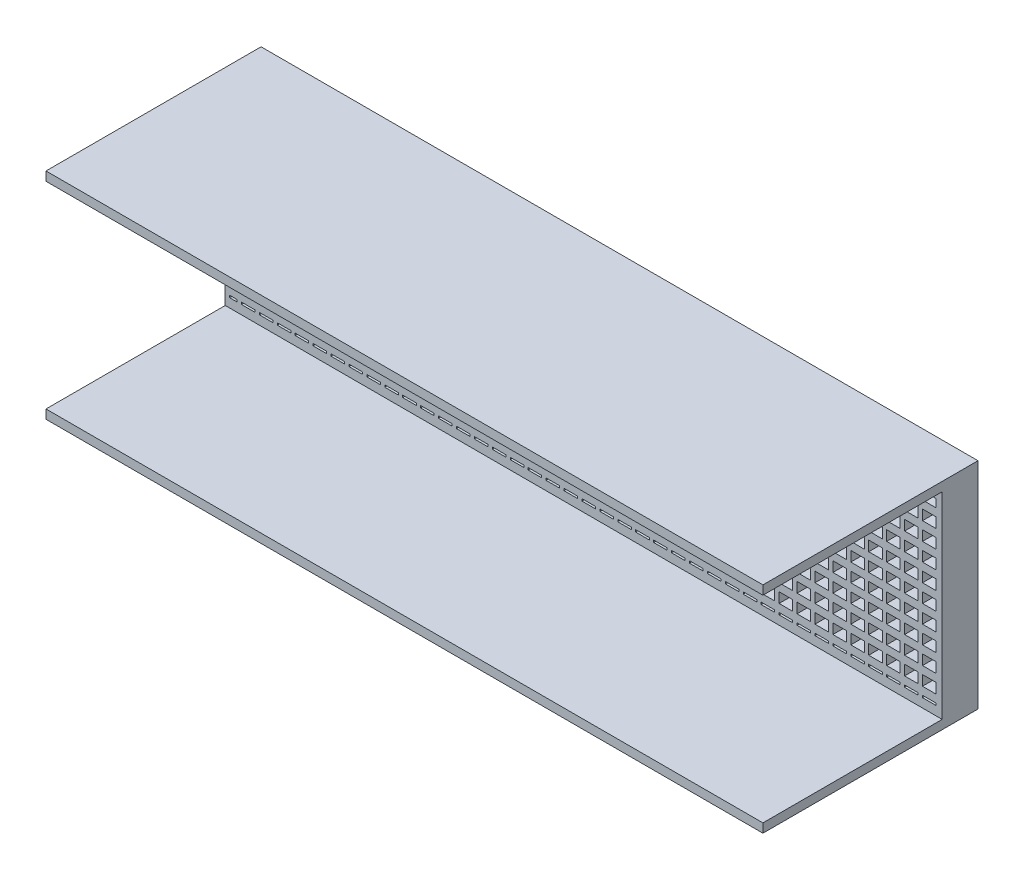
SolidWorks part; units mm, degrees
ref_plane "Plan de face" through (0, 0, 0) normal (0, 0, 1) x (1, 0, 0)
ref_plane "Plan de dessus" through (0, 0, 0) normal (0, 1, 0) x (1, 0, 0)
ref_plane "Plan de droite" through (0, 0, 0) normal (1, 0, 0) x (0, 0, -1)
sketch "Esquisse1" plane through (0, 0, 0) normal (0, 0, 1) x (1, 0, 0)
  line L1 (-200, 60) -> (200, 60)
  line L2 (-200, 60) -> (-200, -60)
  line L3 (-200, -60) -> (200, -60)
  line L4 (200, 60) -> (200, -60)
  line L5 (-200, 60) -> (200, -60) construction
  line L6 (-200, -60) -> (200, 60) construction
  line L7 (-197.5, 50) -> (197.5, 50)
  line L8 (-197.5, 50) -> (-197.5, -50)
  line L9 (-197.5, -50) -> (197.5, -50)
  line L10 (197.5, 50) -> (197.5, -50)
  line L11 (-197.5, 50) -> (197.5, -50) construction
  line L12 (-197.5, -50) -> (197.5, 50) construction
  point P0 (0, 0)
  point P6 (0, 0)
  dimension "D1" = 120
  dimension "D2" = 400
  dimension "D3" = 100
  dimension "D4" = 395
extrude "Boss.-Extru.1" add sketch "Esquisse1" along normal blind 120
sketch "Esquisse2" plane through (200, 0, 0) normal (1, 0, 0) x (0, 0, -1)
  line L0 (-135.8459, 0) -> (-4.1541, 0)
  line L5 (0, -60) -> (0, 60) construction
  line L6 (-120, 55) -> (-20, 55)
  line L7 (-120, 55) -> (-120, -55)
  line L8 (-120, -55) -> (-20, -55)
  line L9 (-20, 55) -> (-20, -55)
  line L10 (-120, 55) -> (-20, -55) construction
  line L11 (-120, -55) -> (-20, 55) construction
  point P11 (-70, 0)
  line M3 (-120, 60) -> (-120, -60)
  dimension "D1" = 100
  dimension "D2" = 20
  dimension "D3" = 110
extrude "Enlèv. mat.-Extru.1" cut sketch "Esquisse2" against normal through all both and the other way through all contours L9 L0 L8 M3 | L9 L6 L0 M3
sketch "Esquisse3" plane through (0, 0, 0) normal (0, 0, 1) x (1, 0, 0)
  line L0 (0, 113.9333) -> (0, -153.2626) construction
  line L1 (-197.5, -50) -> (197.5, -50) construction
  line L2 (-193.4028, 50) -> (-190.97, 50)
  line L3 (-193.4028, 50) -> (-193.4028, -50)
  line L4 (-193.4028, -50) -> (-190.97, -50)
  line L5 (-190.97, 50) -> (-190.97, -50)
  line L6 (-193.4028, 50) -> (-190.97, -50) construction
  line L7 (-193.4028, -50) -> (-190.97, 50) construction
  line L8 (-197.5, 0) -> (197.5, 0) construction
  line L9 (-197.5, 50) -> (-197.5, -50) construction
  line L10 (197.5, -50) -> (197.5, 50) construction
  line L11 (-180.97, 50) -> (-180.97, -50)
  line L12 (-183.4028, 50) -> (-183.4028, -50)
  line L13 (-183.4028, -50) -> (-180.97, -50)
  line L14 (-183.4028, 50) -> (-180.97, 50)
  line L15 (-170.97, 50) -> (-170.97, -50)
  line L16 (-173.4028, 50) -> (-173.4028, -50)
  line L17 (-173.4028, -50) -> (-170.97, -50)
  line L18 (-173.4028, 50) -> (-170.97, 50)
  line L19 (-160.97, 50) -> (-160.97, -50)
  line L20 (-163.4028, 50) -> (-163.4028, -50)
  line L21 (-163.4028, -50) -> (-160.97, -50)
  line L22 (-163.4028, 50) -> (-160.97, 50)
  line L23 (-150.97, 50) -> (-150.97, -50)
  line L24 (-153.4028, 50) -> (-153.4028, -50)
  line L25 (-153.4028, -50) -> (-150.97, -50)
  line L26 (-153.4028, 50) -> (-150.97, 50)
  line L27 (-140.97, 50) -> (-140.97, -50)
  line L28 (-143.4028, 50) -> (-143.4028, -50)
  line L29 (-143.4028, -50) -> (-140.97, -50)
  line L30 (-143.4028, 50) -> (-140.97, 50)
  line L31 (-130.97, 50) -> (-130.97, -50)
  line L32 (-133.4028, 50) -> (-133.4028, -50)
  line L33 (-133.4028, -50) -> (-130.97, -50)
  line L34 (-133.4028, 50) -> (-130.97, 50)
  line L35 (-120.97, 50) -> (-120.97, -50)
  line L36 (-123.4028, 50) -> (-123.4028, -50)
  line L37 (-123.4028, -50) -> (-120.97, -50)
  line L38 (-123.4028, 50) -> (-120.97, 50)
  line L39 (-110.97, 50) -> (-110.97, -50)
  line L40 (-113.4028, 50) -> (-113.4028, -50)
  line L41 (-113.4028, -50) -> (-110.97, -50)
  line L42 (-113.4028, 50) -> (-110.97, 50)
  line L43 (-100.97, 50) -> (-100.97, -50)
  line L44 (-103.4028, 50) -> (-103.4028, -50)
  line L45 (-103.4028, -50) -> (-100.97, -50)
  line L46 (-103.4028, 50) -> (-100.97, 50)
  line L47 (-90.97, 50) -> (-90.97, -50)
  line L48 (-93.4028, 50) -> (-93.4028, -50)
  line L49 (-93.4028, -50) -> (-90.97, -50)
  line L50 (-93.4028, 50) -> (-90.97, 50)
  line L51 (-80.97, 50) -> (-80.97, -50)
  line L52 (-83.4028, 50) -> (-83.4028, -50)
  line L53 (-83.4028, -50) -> (-80.97, -50)
  line L54 (-83.4028, 50) -> (-80.97, 50)
  line L55 (-70.97, 50) -> (-70.97, -50)
  line L56 (-73.4028, 50) -> (-73.4028, -50)
  line L57 (-73.4028, -50) -> (-70.97, -50)
  line L58 (-73.4028, 50) -> (-70.97, 50)
  line L59 (-60.97, 50) -> (-60.97, -50)
  line L60 (-63.4028, 50) -> (-63.4028, -50)
  line L61 (-63.4028, -50) -> (-60.97, -50)
  line L62 (-63.4028, 50) -> (-60.97, 50)
  line L63 (-50.97, 50) -> (-50.97, -50)
  line L64 (-53.4028, 50) -> (-53.4028, -50)
  line L65 (-53.4028, -50) -> (-50.97, -50)
  line L66 (-53.4028, 50) -> (-50.97, 50)
  line L67 (-40.97, 50) -> (-40.97, -50)
  line L68 (-43.4028, 50) -> (-43.4028, -50)
  line L69 (-43.4028, -50) -> (-40.97, -50)
  line L70 (-43.4028, 50) -> (-40.97, 50)
  line L71 (-30.97, 50) -> (-30.97, -50)
  line L72 (-33.4028, 50) -> (-33.4028, -50)
  line L73 (-33.4028, -50) -> (-30.97, -50)
  line L74 (-33.4028, 50) -> (-30.97, 50)
  line L75 (-20.97, 50) -> (-20.97, -50)
  line L76 (-23.4028, 50) -> (-23.4028, -50)
  line L77 (-23.4028, -50) -> (-20.97, -50)
  line L78 (-23.4028, 50) -> (-20.97, 50)
  line L79 (-10.97, 50) -> (-10.97, -50)
  line L80 (-13.4028, 50) -> (-13.4028, -50)
  line L81 (-13.4028, -50) -> (-10.97, -50)
  line L82 (-13.4028, 50) -> (-10.97, 50)
  line L83 (-0.97, 50) -> (-0.97, -50)
  line L84 (-3.4028, 50) -> (-3.4028, -50)
  line L85 (-3.4028, -50) -> (-0.97, -50)
  line L86 (-3.4028, 50) -> (-0.97, 50)
  line L87 (9.03, 50) -> (9.03, -50)
  line L88 (6.5972, 50) -> (6.5972, -50)
  line L89 (6.5972, -50) -> (9.03, -50)
  line L90 (6.5972, 50) -> (9.03, 50)
  line L91 (19.03, 50) -> (19.03, -50)
  line L92 (16.5972, 50) -> (16.5972, -50)
  line L93 (16.5972, -50) -> (19.03, -50)
  line L94 (16.5972, 50) -> (19.03, 50)
  line L95 (29.03, 50) -> (29.03, -50)
  line L96 (26.5972, 50) -> (26.5972, -50)
  line L97 (26.5972, -50) -> (29.03, -50)
  line L98 (26.5972, 50) -> (29.03, 50)
  line L99 (39.03, 50) -> (39.03, -50)
  line L100 (36.5972, 50) -> (36.5972, -50)
  line L101 (36.5972, -50) -> (39.03, -50)
  line L102 (36.5972, 50) -> (39.03, 50)
  line L103 (49.03, 50) -> (49.03, -50)
  line L104 (46.5972, 50) -> (46.5972, -50)
  line L105 (46.5972, -50) -> (49.03, -50)
  line L106 (46.5972, 50) -> (49.03, 50)
  line L107 (59.03, 50) -> (59.03, -50)
  line L108 (56.5972, 50) -> (56.5972, -50)
  line L109 (56.5972, -50) -> (59.03, -50)
  line L110 (56.5972, 50) -> (59.03, 50)
  line L111 (69.03, 50) -> (69.03, -50)
  line L112 (66.5972, 50) -> (66.5972, -50)
  line L113 (66.5972, -50) -> (69.03, -50)
  line L114 (66.5972, 50) -> (69.03, 50)
  line L115 (79.03, 50) -> (79.03, -50)
  line L116 (76.5972, 50) -> (76.5972, -50)
  line L117 (76.5972, -50) -> (79.03, -50)
  line L118 (76.5972, 50) -> (79.03, 50)
  line L119 (89.03, 50) -> (89.03, -50)
  line L120 (86.5972, 50) -> (86.5972, -50)
  line L121 (86.5972, -50) -> (89.03, -50)
  line L122 (86.5972, 50) -> (89.03, 50)
  line L123 (99.03, 50) -> (99.03, -50)
  line L124 (96.5972, 50) -> (96.5972, -50)
  line L125 (96.5972, -50) -> (99.03, -50)
  line L126 (96.5972, 50) -> (99.03, 50)
  line L127 (109.03, 50) -> (109.03, -50)
  line L128 (106.5972, 50) -> (106.5972, -50)
  line L129 (106.5972, -50) -> (109.03, -50)
  line L130 (106.5972, 50) -> (109.03, 50)
  line L131 (119.03, 50) -> (119.03, -50)
  line L132 (116.5972, 50) -> (116.5972, -50)
  line L133 (116.5972, -50) -> (119.03, -50)
  line L134 (116.5972, 50) -> (119.03, 50)
  line L135 (129.03, 50) -> (129.03, -50)
  line L136 (126.5972, 50) -> (126.5972, -50)
  line L137 (126.5972, -50) -> (129.03, -50)
  line L138 (126.5972, 50) -> (129.03, 50)
  line L139 (139.03, 50) -> (139.03, -50)
  line L140 (136.5972, 50) -> (136.5972, -50)
  line L141 (136.5972, -50) -> (139.03, -50)
  line L142 (136.5972, 50) -> (139.03, 50)
  line L143 (149.03, 50) -> (149.03, -50)
  line L144 (146.5972, 50) -> (146.5972, -50)
  line L145 (146.5972, -50) -> (149.03, -50)
  line L146 (146.5972, 50) -> (149.03, 50)
  line L147 (159.03, 50) -> (159.03, -50)
  line L148 (156.5972, 50) -> (156.5972, -50)
  line L149 (156.5972, -50) -> (159.03, -50)
  line L150 (156.5972, 50) -> (159.03, 50)
  line L151 (169.03, 50) -> (169.03, -50)
  line L152 (166.5972, 50) -> (166.5972, -50)
  line L153 (166.5972, -50) -> (169.03, -50)
  line L154 (166.5972, 50) -> (169.03, 50)
  line L155 (179.03, 50) -> (179.03, -50)
  line L156 (176.5972, 50) -> (176.5972, -50)
  line L157 (176.5972, -50) -> (179.03, -50)
  line L158 (176.5972, 50) -> (179.03, 50)
  line L159 (189.03, 50) -> (189.03, -50)
  line L160 (186.5972, 50) -> (186.5972, -50)
  line L161 (186.5972, -50) -> (189.03, -50)
  line L162 (186.5972, 50) -> (189.03, 50)
  line L163 (199.03, 50) -> (199.03, -50)
  line L164 (196.5972, 50) -> (196.5972, -50)
  line L165 (196.5972, -50) -> (199.03, -50)
  line L166 (196.5972, 50) -> (199.03, 50)
  point P3 (-192.1864, 0)
  dimension "D1" = 40
extrude "Boss.-Extru.2" add sketch "Esquisse3" along normal blind 20
sketch "Esquisse4" plane through (0, 0, 0) normal (0, 0, 1) x (1, 0, 0)
  line L0 (-214.8731, 0) -> (274.7967, 0) construction
  line L5 (-197.5, 50) -> (-197.5, -50) construction
  line L6 (-197.5, 45.5238) -> (196.5972, 45.5238)
  line L10 (-197.5, 45.5238) -> (-197.5, 41.1839)
  line L11 (-197.5, 41.1839) -> (196.5972, 41.1839)
  line L12 (196.5972, 45.5238) -> (196.5972, 41.1839)
  line L13 (196.5972, 50) -> (196.5972, -50) construction
  line L15 (-197.5, 31.1839) -> (196.5972, 31.1839)
  line L16 (-197.5, 35.5238) -> (196.5972, 35.5238)
  line L17 (-197.5, 35.5238) -> (-197.5, 31.1839)
  line L18 (196.5972, 35.5238) -> (196.5972, 31.1839)
  line L19 (-197.5, 21.1839) -> (196.5972, 21.1839)
  line L20 (-197.5, 25.5238) -> (196.5972, 25.5238)
  line L21 (-197.5, 25.5238) -> (-197.5, 21.1839)
  line L22 (196.5972, 25.5238) -> (196.5972, 21.1839)
  line L23 (-197.5, 11.1839) -> (196.5972, 11.1839)
  line L24 (-197.5, 15.5238) -> (196.5972, 15.5238)
  line L25 (-197.5, 15.5238) -> (-197.5, 11.1839)
  line L26 (196.5972, 15.5238) -> (196.5972, 11.1839)
  line L27 (-197.5, 1.1839) -> (196.5972, 1.1839)
  line L28 (-197.5, 5.5238) -> (196.5972, 5.5238)
  line L29 (-197.5, 5.5238) -> (-197.5, 1.1839)
  line L30 (196.5972, 5.5238) -> (196.5972, 1.1839)
  line L31 (-197.5, -8.8161) -> (196.5972, -8.8161)
  line L32 (-197.5, -4.4762) -> (196.5972, -4.4762)
  line L33 (-197.5, -4.4762) -> (-197.5, -8.8161)
  line L34 (196.5972, -4.4762) -> (196.5972, -8.8161)
  line L35 (-197.5, -18.8161) -> (196.5972, -18.8161)
  line L36 (-197.5, -14.4762) -> (196.5972, -14.4762)
  line L37 (-197.5, -14.4762) -> (-197.5, -18.8161)
  line L38 (196.5972, -14.4762) -> (196.5972, -18.8161)
  line L39 (-197.5, -28.8161) -> (196.5972, -28.8161)
  line L40 (-197.5, -24.4762) -> (196.5972, -24.4762)
  line L41 (-197.5, -24.4762) -> (-197.5, -28.8161)
  line L42 (196.5972, -24.4762) -> (196.5972, -28.8161)
  line L43 (-197.5, -38.8161) -> (196.5972, -38.8161)
  line L44 (-197.5, -34.4762) -> (196.5972, -34.4762)
  line L45 (-197.5, -34.4762) -> (-197.5, -38.8161)
  line L46 (196.5972, -34.4762) -> (196.5972, -38.8161)
  line L47 (-197.5, -48.8161) -> (196.5972, -48.8161)
  line L48 (-197.5, -44.4762) -> (196.5972, -44.4762)
  line L49 (-197.5, -44.4762) -> (-197.5, -48.8161)
  line L50 (196.5972, -44.4762) -> (196.5972, -48.8161)
  dimension "D1" = 10
extrude "Boss.-Extru.3" add sketch "Esquisse4" along normal blind 20
